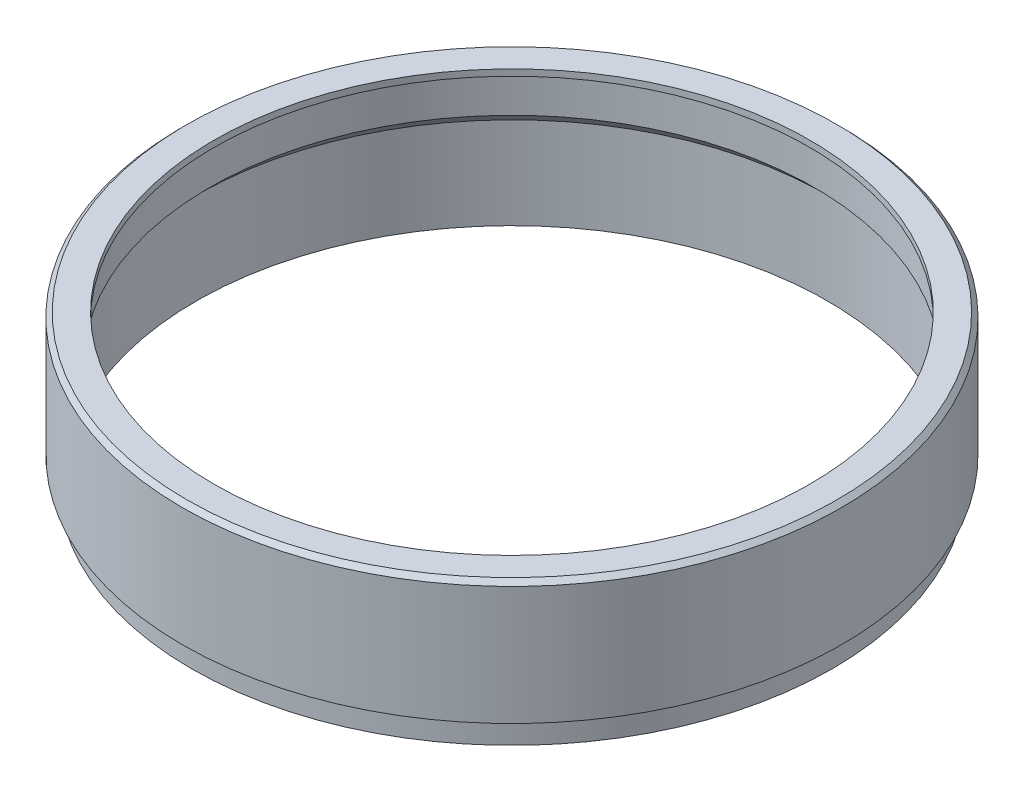
SolidWorks part; units mm, degrees
ref_plane "Front Plane" through (0, 0, 0) normal (0, 0, 1) x (1, 0, 0)
ref_plane "Top Plane" through (0, 0, 0) normal (0, 1, 0) x (1, 0, 0)
ref_plane "Right Plane" through (0, 0, 0) normal (1, 0, 0) x (0, 0, -1)
ref_axis "Axis1" through (0, 0, 0) along (0, 1, 0)
sketch "Sketch1" plane through (0, 0, 0) normal (0, 0, 1) x (1, 0, 0)
  line L0 (0, 0) -> (0, -50000) construction
  line L1 (-35, 3.2) -> (-35, 13.35)
  line L2 (-35, 13.35) -> (-33.5, 14.85)
  line L3 (-33.5, 14.85) -> (-33.5, 18.95)
  line L4 (-33.5, 18.95) -> (-33, 18.95)
  line L5 (-33, 18.95) -> (-33, 19.65)
  line L6 (-33, 19.65) -> (-36, 19.65)
  line L7 (-36, 19.65) -> (-36.5, 19.15)
  line L8 (-36.5, 19.15) -> (-36.5, 6)
  line L9 (-36.5, 6) -> (-35.5, 6)
  line L10 (-35.5, 6) -> (-35.5, 3.2)
  line L11 (-35.5, 3.2) -> (-35, 3.2)
  line L12 (-35, -9) -> (-35, 3) construction
  line L13 (-36.5, 6) -> (-36.5, -11.2) construction
  line L15 (35.55, 6) -> (-35.55, 6) construction
  line L18 (-35, 3) -> (-35.55, 3) construction
  line L20 (33.5, 18.95) -> (-33.5, 18.95) construction
  dimension "D1" = 0.2
  dimension "D2" = 67
  dimension "D3" = 0.5
  dimension "D4" = 0.7
  dimension "D5" = 135
  dimension "D6" = 0.5
  dimension "D7" = 135
  dimension "D8" = 4.1
  dimension "D9" = 71
revolve "Revolve1" add sketch "Sketch1" angle 360 about L0
